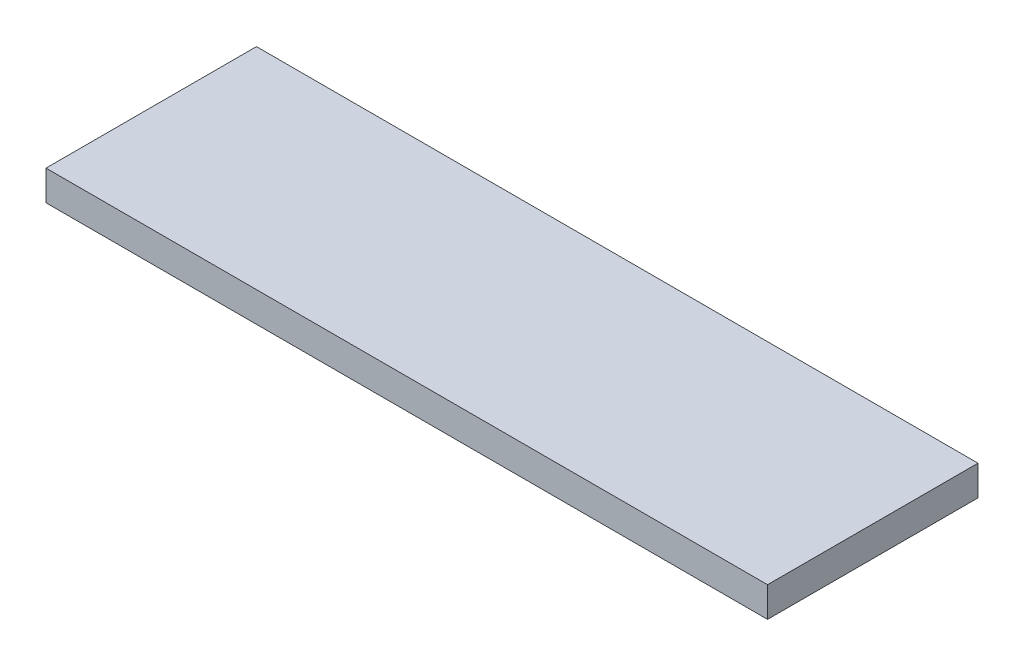
SolidWorks part; units mm, degrees
ref_plane "Front Plane" through (0, 0, 0) normal (0, 0, 1) x (1, 0, 0)
ref_plane "Top Plane" through (0, 0, 0) normal (0, 1, 0) x (1, 0, 0)
ref_plane "Right Plane" through (0, 0, 0) normal (1, 0, 0) x (0, 0, -1)
sketch "Sketch1" plane through (0, 0, 0) normal (0, 1, 0) x (1, 0, 0)
  line L1 (-52.2265, 71.5031) -> (252.5735, 71.5031)
  line L2 (-52.2265, 71.5031) -> (-52.2265, -17.3969)
  line L3 (-52.2265, -17.3969) -> (252.5735, -17.3969)
  line L4 (252.5735, 71.5031) -> (252.5735, -17.3969)
  dimension "D1" = 88.9
  dimension "D2" = 304.8
extrude "Boss-Extrude1" add sketch "Sketch1" along normal blind 12.7
